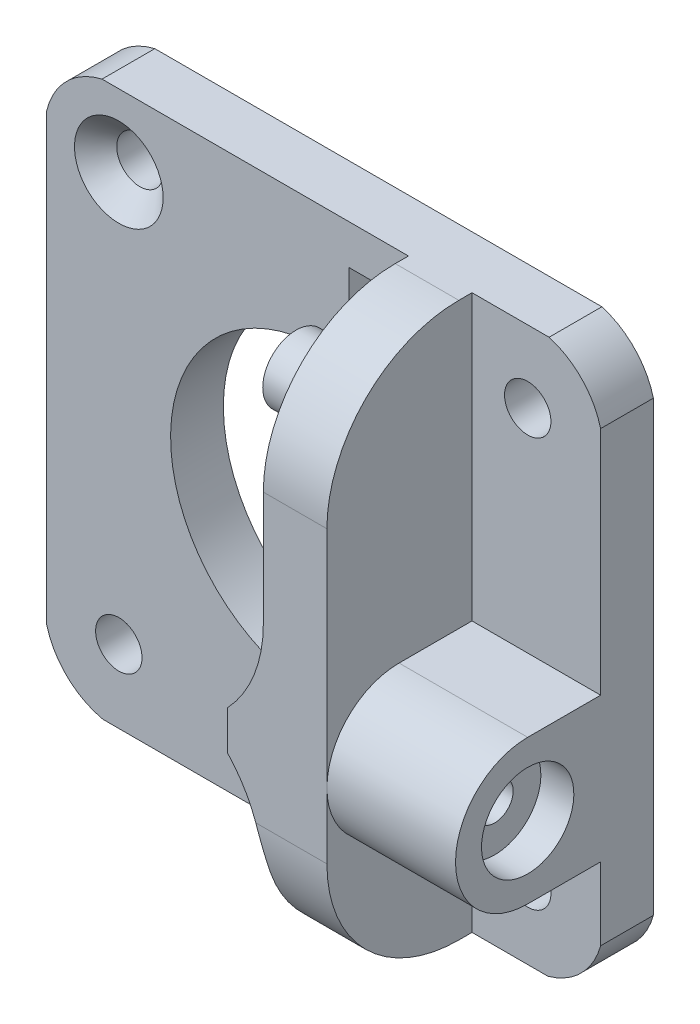
SolidWorks part; units mm, degrees
ref_plane "Alzado" through (0, 0, 0) normal (0, 0, 1) x (1, 0, 0)
ref_plane "Planta" through (0, 0, 0) normal (0, 1, 0) x (1, 0, 0)
ref_plane "Vista lateral" through (0, 0, 0) normal (1, 0, 0) x (0, 0, -1)
sketch "Croquis2" plane through (0, 0, 0) normal (0, 0, 1) x (1, 0, 0)
  line L0 (19.3659, 0) -> (-41.5127, 0) construction
  line L1 (-6.6318, -21.105) -> (27.1021, -21.105) construction
  line L2 (-6.6991, 20.895) -> (27.1943, 20.895) construction
  line L3 (44.6535, 0) -> (-37.738, 0) construction
  line L4 (-10.9015, -17.0099) -> (-10.9015, 16.6926) construction
  line L5 (10.0548, -36.289) -> (10.0548, 32.8928) construction
  line L6 (25.571, 15.4225) -> (-5.429, 15.4225) construction
  line L7 (-5.429, 15.4225) -> (-5.429, -15.5775) construction
  line L8 (-5.429, -15.5775) -> (25.571, -15.5775) construction
  line L9 (-10.9015, 16.6926) -> (-10.9015, -17.0099)
  line L10 (-6.6318, -21.105) -> (27.1021, -21.105)
  line L11 (31.0985, -17.1086) -> (31.0985, 16.8473)
  line L12 (27.1943, 20.895) -> (-6.6991, 20.895)
  line L13 (20.3633, -5.226) -> (21.35, -5.226)
  line L14 (21.35, -5.226) -> (21.35, 5.226)
  line L15 (21.35, 5.226) -> (20.3633, 5.226)
  line L17 (16.526, 9.576) -> (16.526, 17.886)
  line L18 (16.526, 17.886) -> (12.011, 17.886)
  line L19 (12.011, 17.886) -> (12.011, 11.3908)
  line L22 (31.0985, -17.1086) -> (31.0985, 16.8473) construction
  line L23 (25.571, -15.5775) -> (25.571, 15.4225) construction
  circle A0 centre (-5.429, 15.4225) radius 1.7588
  circle A1 centre (25.571, 15.4225) radius 1.7588
  circle A2 centre (25.571, -15.5775) radius 1.7588
  circle A3 centre (-5.429, -15.5775) radius 1.7588
  arc A5 (20.3633, 5.226) -> (16.526, 9.576) centre (10.0548, 0) ccw
  arc A6 (12.011, 11.3908) -> (20.3633, -5.226) centre (10.0548, 0) ccw
  arc A7 (27.1021, -21.105) -> (31.0985, -17.1086) centre (25.571, -15.5775) ccw
  arc A8 (-10.9015, -17.0099) -> (-6.6318, -21.105) centre (-5.429, -15.5775) ccw
  arc A9 (-6.6991, 20.895) -> (-10.9015, 16.6926) centre (-5.429, 15.4225) ccw
  arc A10 (31.0985, 16.8473) -> (27.1943, 20.895) centre (25.571, 15.4225) ccw
  dimension "D2" = 11.5575
  dimension "D1" = 20.9563
  dimension "D3" = 20.895
  dimension "D4" = 10.452
  dimension "D5" = 42
  dimension "D6" = 42
  dimension "D7" = 5.4725
  dimension "D8" = 5.5275
extrude "Saliente-Extruir1" add sketch "Croquis2" along normal blind 4
sketch "Croquis3" plane through (0, 0, 4) normal (0, 0, 1) x (1, 0, 0)
  line L0 (16.5285, -21.105) -> (21.3485, -21.105)
  line L1 (-6.6318, -21.105) -> (27.1021, -21.105) construction
  line L2 (21.3485, -21.105) -> (21.3485, 20.895)
  line L3 (27.1943, 20.895) -> (-6.6991, 20.895) construction
  line L4 (21.3485, 20.895) -> (16.5285, 20.895)
  line L5 (16.5285, 20.895) -> (16.5285, -21.105)
  line L6 (31.0985, -17.1086) -> (31.0985, 16.8473) construction
  dimension "D1" = 9.75
  dimension "D2" = 4.82
extrude "Saliente-Extruir2" add sketch "Croquis3" along normal blind 11
sketch "Croquis5" plane through (16.5285, 0, 0) normal (-1, 0, 0) x (0, 0, 1)
  line L0 (4, 16.6926) -> (4, -17.0099) construction
  line L2 (15, 20.895) -> (4, 20.895) construction
  circle A0 centre (9.53, 14.775) radius 2.515
  point P0 (9.53, 14.775)
  dimension "D1" = 5.53
  dimension "D2" = 6.12
extrude "Saliente-Extruir3" add sketch "Croquis5" along normal blind 3
sketch "Croquis6" plane through (0, 0, 15) normal (0, 0, 1) x (1, 0, 0)
  line L0 (16.5285, -7.605) -> (13.8285, -7.605)
  line L1 (16.5285, -9.5743) -> (16.5285, -21.105) construction
  line L2 (13.8285, -7.605) -> (13.8285, -4.605)
  line L3 (13.8285, -4.605) -> (16.5285, -4.605)
  line L4 (16.5285, 20.895) -> (16.5285, -21.105) construction
  line L5 (16.5285, -7.605) -> (16.5285, -4.605)
  line L6 (13.8285, -6.105) -> (16.5285, -6.105) construction
  line L7 (-6.6318, -21.105) -> (16.5285, -21.105) construction
  dimension "D1" = 2.7
  dimension "D2" = 15
  dimension "D3" = 3
extrude "Saliente-Extruir4" add sketch "Croquis6" against normal up to surface (11 mm away) up to face at (5.9468, 4.3881, 4)
sketch "Croquis8" plane through (13.8285, 0, 0) normal (-1, 0, 0) x (0, 0, 1)
  circle A0 centre (9.53, -6.125) radius 1.4
  point P0 (9.53, -6.125)
  point P2 (9.53, 14.775)
  dimension "D1" = 20.9
fillet "Redondeo1" radius 10 2 edges at (16.5285, -4.605, 9.5) (16.5285, -7.605, 9.5)
extrude "Cortar-Extruir1" cut sketch "Croquis8" against normal up to next
fillet "Redondeo2" radius 10 2 edges at (18.9385, 20.895, 15) (18.9385, -21.105, 15)
sketch "Croquis9" plane through (21.3485, 0, 0) normal (1, 0, 0) x (0, 0, -1)
  line L0 (-9.53, -0.655) -> (-4, -0.655)
  line L1 (-4, -5.226) -> (-4, 5.226) construction
  line L2 (-4, -11.595) -> (-4, -0.655)
  line L3 (-4, -17.1086) -> (-4, 16.8473) construction
  line L4 (-4, -11.595) -> (-9.53, -11.595)
  arc A0 (-9.53, -0.655) -> (-9.53, -11.595) centre (-9.53, -6.125) ccw
  circle A1 centre (-9.53, -6.125) radius 1.4
extrude "Saliente-Extruir5" add sketch "Croquis9" along normal up to surface (9.75 mm away) up to face at (31.0985, -0.1307, 2)
sketch "Croquis10" plane through (31.0985, 0, 0) normal (1, 0, 0) x (0, 0, -1)
  circle A0 centre (-9.53, -6.125) radius 3.5
extrude "Cortar-Extruir2" cut sketch "Croquis10" against normal blind 2.5
sketch "Croquis11" plane through (0, 0, 4) normal (0, 0, 1) x (1, 0, 0)
  point P0 (-5.429, 15.4225)
hole_wizard "Refrentado para tornillo tapón con cabeza plana de clavija de M31" positions "Croquis12" profile "Croquis13" countersink size "M3" standard "Ansi Metric" end condition through all
sketch "Croquis12" plane through (0, 0, 4) normal (0, 0, 1) x (1, 0, 0)
  point P0 (-5.429, 15.4225)
sketch "Croquis13" plane through (-5.429, 15.4225, 4) normal (1, 0, 0) x (0, -1, 0)
  line L0 (0, 0) -> (0, 4)
  line L1 (0, 4) -> (1.65, 4)
  line L2 (1.65, 4) -> (1.65, 1.71)
  line L3 (1.65, 1.71) -> (3.36, 0)
  line L5 (3.36, 0) -> (0, 0)
  line L6 (-1.65, 1.71) -> (-3.36, 0) construction
  line L11 (0, -6.35) -> (0, 107.95) construction
  dimension "Diámetro de taladro hasta el siguiente" = 3.3
  dimension "Profundidad de taladro hasta el siguiente" = 4
  dimension "Diámetro de avellanado cercano" = 6.72
  dimension "Ángulo de avellanado cercano" = 90
